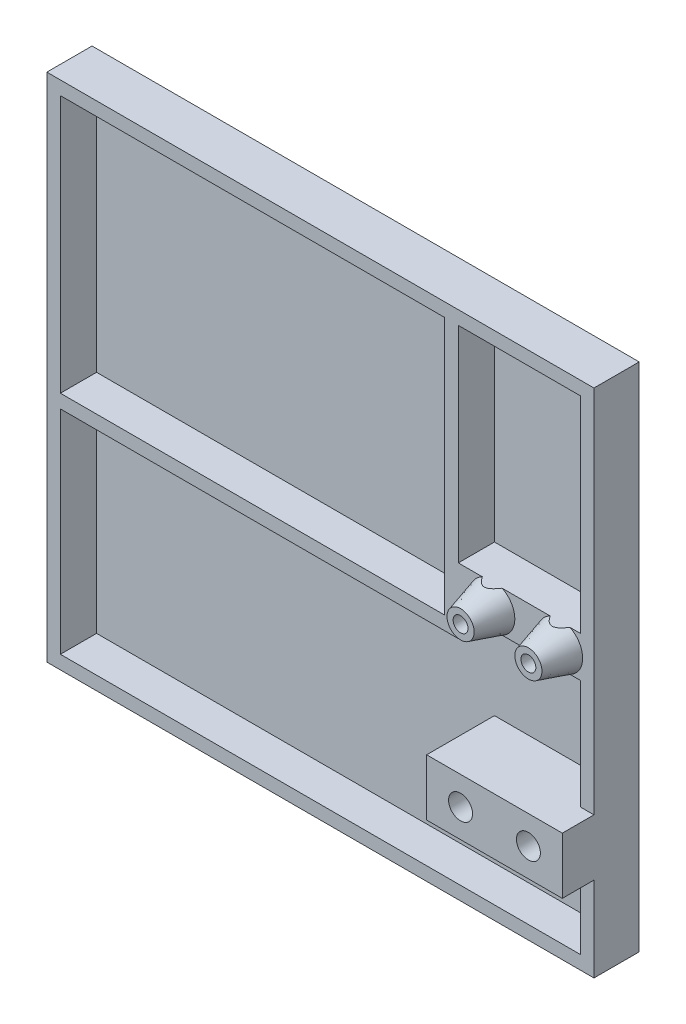
SolidWorks part; units mm, degrees
material "ABS"
ref_plane "Front Plane" through (0, 0, 0) normal (0, 0, 1) x (1, 0, 0)
ref_plane "Top Plane" through (0, 0, 0) normal (0, 1, 0) x (1, 0, 0)
ref_plane "Right Plane" through (0, 0, 0) normal (1, 0, 0) x (0, 0, -1)
sketch "Sketch1" plane through (0, 0, 0) normal (0, 0, 1) x (1, 0, 0)
  line L0 (-45.5, -31.5) -> (-45.5, 31.5) construction
  line L1 (-42.5, -28.5) -> (42.5, -28.5)
  line L2 (-42.5, -28.5) -> (-42.5, 28.5)
  line L3 (-42.5, 28.5) -> (42.5, 28.5)
  line L4 (42.5, -28.5) -> (42.5, 28.5)
  line L5 (-42.5, -28.5) -> (42.5, 28.5) construction
  line L6 (-42.5, 28.5) -> (42.5, -28.5) construction
  line L7 (-45.5, -81.5) -> (75.5, -81.5) construction
  line L8 (-45.5, -81.5) -> (-45.5, -31.5) construction
  line L9 (-45.5, -31.5) -> (75.5, -31.5) construction
  line L10 (75.5, -81.5) -> (75.5, -31.5) construction
  line L11 (-45.5, -81.5) -> (75.5, -31.5) construction
  line L12 (-45.5, -31.5) -> (75.5, -81.5) construction
  line L17 (-45.5, 31.5) -> (45.5, 31.5) construction
  line L18 (45.5, -31.5) -> (45.5, 31.5) construction
  line L19 (-45.5, -31.5) -> (45.5, -31.5) construction
  line L21 (45.5, 31.5) -> (75.5, 31.5) construction
  line L22 (45.5, 31.5) -> (45.5, -31.5) construction
  line L23 (45.5, -31.5) -> (75.5, -31.5) construction
  line L24 (75.5, 31.5) -> (75.5, -31.5) construction
  line L25 (-45.5, 31.5) -> (75.5, 31.5)
  line L26 (-45.5, 31.5) -> (-45.5, -81.5)
  line L27 (-45.5, -81.5) -> (75.5, -81.5)
  line L28 (75.5, 31.5) -> (75.5, -81.5)
  circle A0 centre (68, -56.5) radius 2.65
  circle A1 centre (53, -56.5) radius 2.65
  circle A2 centre (53, -21.5) radius 1.65
  circle A3 centre (68, -21.5) radius 1.65
  point P0 (0, 0)
  point P6 (15, -56.5)
  dimension "D4" = 15
  dimension "D5" = 7.5
  dimension "D6" = 5.3
  dimension "D10" = 3.3
  dimension "D1" = 85
  dimension "D2" = 57
  dimension "D3" = 50
  dimension "D7" = 30
  dimension "D8" = 10
  dimension "D9" = 3
extrude "Boss-Extrude1" add sketch "Sketch1" along normal blind 10
sketch "Sketch2" plane through (0, 0, 0) normal (0, 0, -1) x (-1, 0, 0)
  line L1 (-42.5, 28.5) -> (42.5, 28.5)
  line L2 (-42.5, 28.5) -> (-42.5, -28.5)
  line L3 (-42.5, -28.5) -> (42.5, -28.5)
  line L4 (42.5, 28.5) -> (42.5, -28.5)
extrude "Boss-Extrude2" add sketch "Sketch2" against normal blind 2
sketch "Sketch4" plane through (0, 0, 10) normal (0, 0, 1) x (1, 0, 0)
  line L0 (-42.5, 28.5) -> (-45.5, 31.5) construction
  line L1 (-45.5, 31.5) -> (45.5, 31.5)
  line L2 (-45.5, 31.5) -> (-45.5, -31.5)
  line L3 (-45.5, -31.5) -> (45.5, -31.5)
  line L4 (45.5, 31.5) -> (45.5, -31.5)
  line L5 (42.5, -28.5) -> (45.5, -31.5) construction
  line L6 (-45.5, -31.5) -> (-45.5, -81.5)
  line L7 (-45.5, -81.5) -> (75.5, -81.5)
  line L8 (75.5, -81.5) -> (75.5, 31.5)
  line L9 (75.5, 31.5) -> (45.5, 31.5)
  line L10 (45.5, -31.5) -> (45.5, 31.5)
  line L11 (-45.5, -31.5) -> (45.5, -31.5)
  line L12 (-45.5, -81.5) -> (-45.5, -31.5)
  line L13 (53, -56.5) -> (68, -56.5) construction
  line L14 (-42.5, -28.5) -> (-42.5, -78.5)
  line L15 (45.5, -62.75) -> (75.5, -62.75)
  line L16 (45.5, -62.75) -> (45.5, -50.25)
  line L17 (45.5, -50.25) -> (75.5, -50.25)
  line L18 (75.5, -62.75) -> (75.5, -50.25)
  line L19 (45.5, -62.75) -> (75.5, -50.25) construction
  line L20 (45.5, -50.25) -> (75.5, -62.75) construction
  line L21 (-42.5, -78.5) -> (72.5, -78.5)
  line L22 (72.5, -78.5) -> (72.5, -62.75)
  line L23 (45.5, 28.5) -> (72.5, 28.5)
  line L24 (72.5, 28.5) -> (72.5, -21.5)
  line L25 (72.5, -21.5) -> (72.5, -50.25)
  line L26 (-42.5, -78.5) -> (-45.5, -81.5) construction
  line L27 (72.5, -78.5) -> (75.5, -81.5) construction
  line L28 (72.5, 28.5) -> (75.5, 31.5) construction
  line L29 (53, -21.5) -> (68, -21.5) construction
  line L31 (75.5, -26) -> (45.5, -26)
  line L32 (75.5, -26) -> (75.5, -17)
  line L33 (75.5, -17) -> (45.5, -17)
  line L34 (45.5, -26) -> (45.5, -17)
  line L35 (75.5, -26) -> (45.5, -17) construction
  line L36 (75.5, -17) -> (45.5, -26) construction
  circle A2 centre (53, -56.5) radius 2.65
  circle A3 centre (68, -56.5) radius 2.65
  circle A6 centre (68, -56.5) radius 2.65 construction
  point P21 (60.5, -56.5)
  point P29 (60.5, -21.5)
  dimension "D2" = 9
  dimension "D1" = 12.5
extrude "Cut-Extrude1" cut sketch "Sketch4" against normal up to surface (8 mm away) contours L33 L24 L23 L10 | L25 L31 L4 L11 L14 L21 L22 L15 L16 L17 region at (59, 5.75, 10) region at (13.4057, -54.1556, 10) up to face at (0, 0, 2)
sketch "Sketch5" plane through (0, 0, 0) normal (0, 0, -1) x (-1, 0, 0)
  line L1 (-64.25, -25.25) -> (-71.75, -25.25)
  line L2 (-64.25, -25.25) -> (-64.25, -17.75)
  line L3 (-64.25, -17.75) -> (-71.75, -17.75)
  line L4 (-71.75, -25.25) -> (-71.75, -17.75)
  line L5 (-64.25, -25.25) -> (-71.75, -17.75) construction
  line L6 (-64.25, -17.75) -> (-71.75, -25.25) construction
  line L7 (-49.25, -25.25) -> (-56.75, -25.25)
  line L8 (-49.25, -25.25) -> (-49.25, -17.75)
  line L9 (-49.25, -17.75) -> (-56.75, -17.75)
  line L10 (-56.75, -25.25) -> (-56.75, -17.75)
  line L11 (-49.25, -25.25) -> (-56.75, -17.75) construction
  line L12 (-49.25, -17.75) -> (-56.75, -25.25) construction
  line L13 (-73.25, -61.75) -> (-62.75, -61.75)
  line L14 (-73.25, -61.75) -> (-73.25, -51.25)
  line L15 (-73.25, -51.25) -> (-62.75, -51.25)
  line L16 (-62.75, -61.75) -> (-62.75, -51.25)
  line L17 (-73.25, -61.75) -> (-62.75, -51.25) construction
  line L18 (-73.25, -51.25) -> (-62.75, -61.75) construction
  line L19 (-47.75, -61.75) -> (-58.25, -61.75)
  line L20 (-47.75, -61.75) -> (-47.75, -51.25)
  line L21 (-47.75, -51.25) -> (-58.25, -51.25)
  line L22 (-58.25, -61.75) -> (-58.25, -51.25)
  line L23 (-47.75, -61.75) -> (-58.25, -51.25) construction
  line L24 (-47.75, -51.25) -> (-58.25, -61.75) construction
  point P0 (-68, -21.5)
  point P6 (-53, -21.5)
  point P12 (-68, -56.5)
  point P18 (-53, -56.5)
  dimension "D1" = 7.5
  dimension "D2" = 10.5
extrude "Cut-Extrude2" cut sketch "Sketch5" against normal blind 7
sketch "Sketch7" plane through (0, 0, 10) normal (0, 0, 1) x (1, 0, 0)
  line L0 (75.5, -81.5) -> (75.5, 31.5) construction
  line L1 (45.5, -50.25) -> (75.5, -50.25)
  line L2 (45.5, -50.25) -> (45.5, -62.75)
  line L3 (45.5, -62.75) -> (75.5, -62.75)
  line L4 (75.5, -50.25) -> (75.5, -62.75)
  line L5 (45.5, -62.75) -> (72.5, -62.75) construction
  circle A0 centre (53, -21.5) radius 1.65
  circle A1 centre (53, -21.5) radius 3
  circle A2 centre (68, -21.5) radius 3
  circle A3 centre (68, -21.5) radius 1.65
  circle A4 centre (53, -56.5) radius 2.65
  circle A5 centre (68, -56.5) radius 2.65
  circle A6 centre (53, -56.5) radius 2.65 construction
  circle A7 centre (53, -21.5) radius 1.65 construction
  dimension "D1" = 6
extrude "Boss-Extrude4" add sketch "Sketch7" along normal blind 7
chamfer "Chamfer2" distance 2 distance2 7 2 edges at (65, -21.5, 10) (50, -21.5, 10) first distance on face at (65, -21.5, 10)
